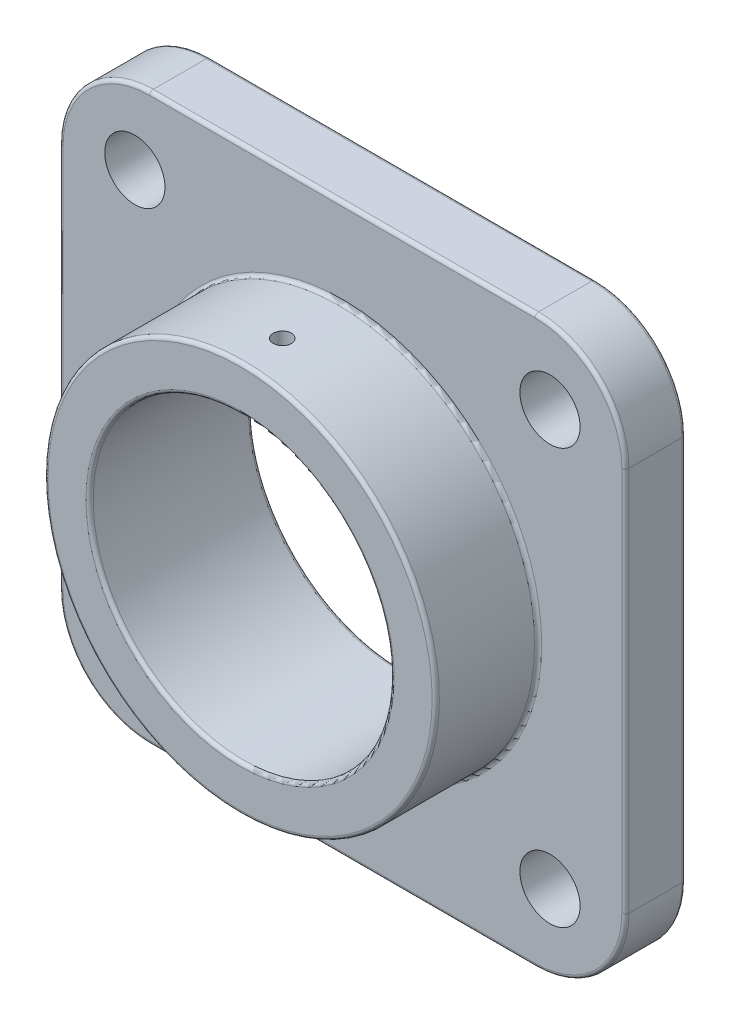
SolidWorks part; units mm, degrees
ref_plane "Ön Düzlem" through (0, 0, 0) normal (0, 0, 1) x (1, 0, 0)
ref_plane "Üst Düzlem" through (0, 0, 0) normal (0, 1, 0) x (1, 0, 0)
ref_plane "Sağ Düzlem" through (0, 0, 0) normal (1, 0, 0) x (0, 0, -1)
sketch "Sketch1" plane through (0, 0, 0) normal (0, 0, 1) x (1, 0, 0)
  line L0 (0, 12.5) -> (0, 25) construction
  line L1 (47, 47) -> (-47, 47)
  line L2 (47, 47) -> (47, -47)
  line L3 (47, -47) -> (-47, -47)
  line L4 (-47, 47) -> (-47, -47)
  line L5 (47, 47) -> (-47, -47) construction
  line L6 (47, -47) -> (-47, 47) construction
  circle A0 centre (0, 0) radius 25
  circle A1 centre (0, 0) radius 12.5 construction
  circle A2 centre (0, 0) radius 32.5
  point P0 (0, 0)
  dimension "D2" = 50
  dimension "D3" = 25
  dimension "D4" = 65
  dimension "D1" = 94
extrude "Boss-Extrude1" add sketch "Sketch1" along normal blind 10 contours L1 L4 L3 L2 A2 region at (45.6706, 0, 0)
extrude "Boss-Extrude2" add sketch "Sketch1<3>" along normal blind 27 contours A2 A0 region at (-31.5808, 0, 0)
sketch "Sketch1<3>" plane through (0, 0, 0) normal (0, 0, 1) x (1, 0, 0) same geometry as "Sketch1"
fillet "Fillet1" radius 15 4 edges at (-47, -47, 5) (47, -47, 5) (-47, 47, 5) (47, 47, 5)
sketch "Sketch2" plane through (0, 0, 10) normal (0, 0, 1) x (1, 0, 0)
  line L0 (0, 0) -> (42.6066, 42.6066) construction
  arc A0 (47, 32) -> (32, 47) centre (32, 32) ccw construction
  circle A1 centre (34.4749, 34.4749) radius 5
  dimension "D1" = 10
  dimension "D2" = 11.5
ref_plane "Plane1" through (0, 59.1782, 0) normal (0, 1, 0) x (1, 0, 0)
sketch "Sketch3" plane through (0, 59.1782, 0) normal (0, 1, 0) x (1, 0, 0)
  circle A0 centre (0, -20) radius 1.5
  dimension "D1" = 3
  dimension "D2" = 20
extrude "Cut-Extrude1" cut sketch "Sketch3" against normal up to next
fillet "Fillet2" radius 0.6 20 edges at (25, 0, 0) (42.6066, -42.6066, 0) (47, 0, 0) (42.6066, 42.6066, 0) (0, 47, 0) (-42.6066, 42.6066, 0) (-47, 0, 0) (-42.6066, -42.6066, 0) (0, -47, 0) (-42.6066, 42.6066, 10) (0, 47, 10) (42.6066, 42.6066, 10) (47, 0, 10) (42.6066, -42.6066, 10) (0, -47, 10) (-42.6066, -42.6066, 10) (-47, 0, 10) (32.5, 0, 10) (25, 0, 27) (32.5, 0, 27)
extrude "Cut-Extrude2" cut sketch "Sketch2" against normal up to next
pattern_circular "CirPattern1" count 4 over 360 about axis through (0, 0, 27) along (0, 0, -1) of "Cut-Extrude2"
